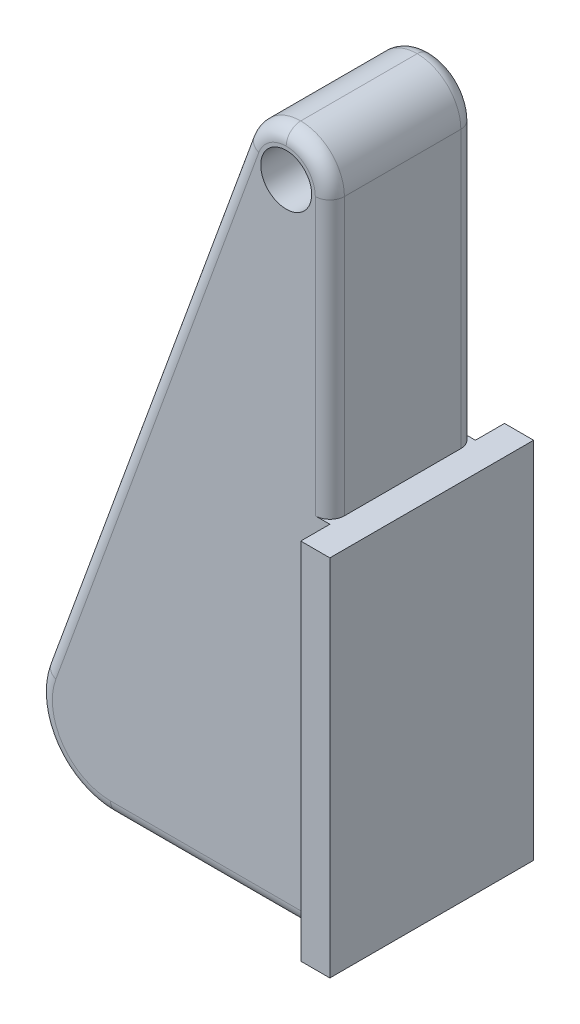
SolidWorks part; units mm, degrees
material "ABS"
ref_plane "Ebene vorne" through (0, 0, 0) normal (0, 0, 1) x (1, 0, 0)
ref_plane "Ebene oben" through (0, 0, 0) normal (0, 1, 0) x (1, 0, 0)
ref_plane "Ebene rechts" through (0, 0, 0) normal (1, 0, 0) x (0, 0, -1)
sketch "Skizze1" plane through (0, 0, 0) normal (0, 0, 1) x (1, 0, 0)
  line L0 (0, 0) -> (0, 47)
  line L1 (0, 47) -> (-5.1006, 47)
  line L2 (-22.2072, 0) -> (0, 0)
  line L3 (-5.1006, 47) -> (-22.2072, 0)
  circle A0 centre (-3, 44) radius 1.75
  dimension "D2" = 3.5
  dimension "D1" = 70
  dimension "D3" = 3
  dimension "D4" = 44
  dimension "D5" = 3
  dimension "D6" = 22.2072
  dimension "D7" = 3
extrude "Aufsatz-Linear austragen1" add sketch "Skizze1" along normal blind 10
sketch "Skizze2" plane through (0, 0, 0) normal (1, 0, 0) x (0, 0, -1)
  line L0 (-10, 0) -> (-10, 47) construction
  line L1 (-12, 25) -> (2, 25)
  line L2 (-12, 25) -> (-12, 0)
  line L3 (-12, 0) -> (2, 0)
  line L4 (2, 25) -> (2, 0)
  line L7 (0, 0) -> (0, 47) construction
  line L10 (-10, 0) -> (0, 0) construction
  line L11 (-10, 47) -> (0, 47) construction
  dimension "D1" = 2
  dimension "D2" = 22
  dimension "D4" = 2
extrude "Aufsatz-Linear austragen2" add sketch "Skizze2" along normal blind 2
fillet "Verrundung5" radius 3 2 edges at (-5.1006, 47, 5) (0, 47, 5)
fillet "Verrundung6" radius 5 1 edges at (-22.2072, 0, 5)
fillet "Verrundung7" radius 1 12 edges at (-4.7207, 46.4575, 0) (-0.8787, 46.1213, 0) (0, 34.5, 0) (0, 34.5, 10) (-4.7207, 46.4575, 10) (-0.8787, 46.1213, 10) (-19.1622, 2.1321, 0) (-19.1622, 2.1321, 10) (-12.792, 25.8681, 0) (-12.792, 25.8681, 10)
